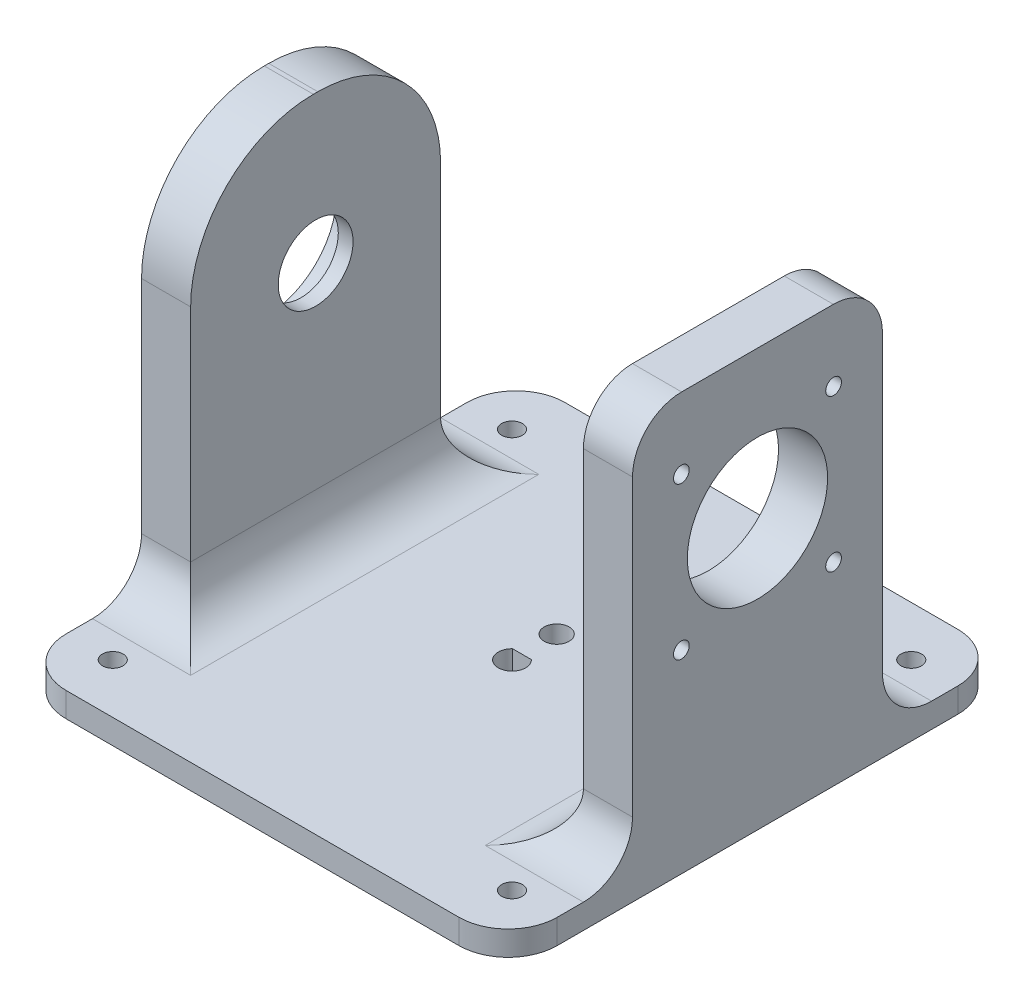
SolidWorks part; units mm, degrees
ref_plane "Front Plane" through (0, 0, 0) normal (0, 0, 1) x (1, 0, 0)
ref_plane "Top Plane" through (0, 0, 0) normal (0, 1, 0) x (1, 0, 0)
ref_plane "Right Plane" through (0, 0, 0) normal (1, 0, 0) x (0, 0, -1)
sketch "Sketch2" plane through (0, 0, 0) normal (0, 1, 0) x (1, 0, 0)
  line L1 (-50, 50.8) -> (50, 50.8)
  line L2 (-50, 50.8) -> (-50, -50.8)
  line L3 (-50, -50.8) -> (50, -50.8)
  line L4 (50, 50.8) -> (50, -50.8)
  line L5 (-50, 50.8) -> (50, -50.8) construction
  line L6 (-50, -50.8) -> (50, 50.8) construction
  line L7 (-50, 50.8) -> (-40, 50.8)
  line L8 (-50, 50.8) -> (-50, -50.8)
  line L9 (-50, -50.8) -> (-40, -50.8)
  line L10 (-40, 50.8) -> (-40, -50.8)
  line L11 (50, 50.8) -> (40, 50.8)
  line L12 (50, 50.8) -> (50, -50.8)
  line L13 (50, -50.8) -> (40, -50.8)
  line L14 (40, 50.8) -> (40, -50.8)
  point P0 (0, 0)
  dimension "D1" = 101.6
  dimension "D2" = 100
  dimension "D3" = 10
  dimension "D4" = 10
extrude "Boss-Extrude1" add sketch "Sketch2" along normal blind 80 contours L10 L1 L2 L3 | L1 L14 L3 L4 region at (-45, 0, 0) region at (45, 0, 0)
extrude "Boss-Extrude2" add sketch "Sketch2<3>" against normal blind 5 contours L1 L14 L3 L4 | L14 L1 L10 L3 | L10 L1 L2 L3 region at (-45, 0, 0) region at (0, 0, 0) region at (45, 0, 0)
sketch "Sketch2<3>" plane through (0, 0, 0) normal (0, 1, 0) x (1, 0, 0) same geometry as "Sketch2"
sketch "Sketch3" plane through (-50, 0, 0) normal (-1, 0, 0) x (0, 0, 1)
  line L0 (0, 80) -> (0, -5) construction
  line L1 (-50.8, 80) -> (50.8, 80) construction
  line L2 (-50.8, -5) -> (50.8, -5) construction
  circle A0 centre (0, 50) radius 14.2875
  dimension "D1" = 28.575
  dimension "D2" = 30
extrude "Cut-Extrude1" cut sketch "Sketch3" against normal blind 117
sketch "Sketch4" plane through (50, 0, 0) normal (1, 0, 0) x (0, 0, -1)
  line L0 (-25.4543, 80) -> (-25.4543, 0)
  line L1 (50.8, 80) -> (-50.8, 80) construction
  line L2 (-25.4543, 0) -> (-50.8, 0)
  line L3 (-50.8, -5) -> (-50.8, 80) construction
  line L4 (0, 80) -> (0, -5) construction
  line L5 (50.8, -5) -> (-50.8, -5) construction
  line L6 (25.4543, 0) -> (50.8, 0)
  line L7 (25.4543, 80) -> (25.4543, 0)
  line L8 (-25.4543, 80) -> (-50.8, 80)
  line L9 (-50.8, 80) -> (-50.8, 0)
  line L10 (25.4543, 80) -> (50.8, 80)
  line L11 (50.8, 80) -> (50.8, 0)
  dimension "D1" = 0
extrude "Cut-Extrude2" cut sketch "Sketch4" against normal blind 119
fillet "Fillet3" radius 10 8 edges at (40, 0, 0) (-40, 0, 0) (-45, 0, -25.4543) (-45, 0, 25.4543) (45, 0, 25.4543) (45, 0, -25.4543) (45, 80, 25.4543) (45, 80, -25.4543)
sketch "Sketch5" plane through (0, 0, 0) normal (0, 1, 0) x (1, 0, 0)
  line L1 (-1.9177, 2.032) -> (1.9177, 2.032)
  arc A0 (-1.9177, 2.032) -> (1.9177, 2.032) centre (0, 0) ccw
  dimension "D1" = 5.588
  dimension "D2" = 2.032
fillet "Fillet2" radius 10 4 edges at (50, -2.5, -50.8) (-50, -2.5, -50.8) (50, -2.5, 50.8) (-50, -2.5, 50.8)
sketch "Sketch7" plane through (50, 0, 0) normal (1, 0, 0) x (0, 0, -1)
  line L0 (0, 87.6521) -> (0, 12.3479) construction
  line L1 (-24.8111, 50) -> (24.8111, 50) construction
  circle A0 centre (-15.5, 65.5) radius 1.6
  circle A1 centre (15.5, 65.5) radius 1.6
  circle A2 centre (15.5, 34.5) radius 1.6
  circle A3 centre (-15.5, 34.5) radius 1.6
  point P5 (0, 50)
  point P8 (0, 50)
  dimension "D1" = 3.2
  dimension "D2" = 15.5
  dimension "D3" = 15.5
extrude "Cut-Extrude4" cut sketch "Sketch7" against normal blind 21
sketch "Sketch8" plane through (40, 0, 0) normal (-1, 0, 0) x (0, 0, 1)
  circle A0 centre (0, 50) radius 14.2875
  circle A1 centre (0, 50) radius 7.62
  dimension "D1" = 15.24
extrude "Boss-Extrude3" add sketch "Sketch8" along normal blind 3 from surface starting at face at (-40, 45, 0)
sketch "Sketch9" plane through (0, -5, 0) normal (0, -1, 0) x (1, 0, 0)
  line L0 (0, 50.8) -> (0, -50.8) construction
  line L2 (-40, -50.8) -> (40, -50.8) construction
  line L3 (-50, 0) -> (50, 0) construction
  line L5 (50, -40.8) -> (50, 40.8) construction
  circle A0 centre (-40.66, 40.66) radius 2.1
  circle A1 centre (40.66, 40.66) radius 2.1
  circle A2 centre (-40.66, -40.66) radius 2.1
  circle A3 centre (40.66, -40.66) radius 2.1
  point P4 (0, 0)
  point P10 (0, 0)
  dimension "D1" = 4.2
  dimension "D2" = 40.66
  dimension "D3" = 40.66
extrude "Cut-Extrude5" cut sketch "Sketch9" against normal up to surface (5 mm away) up to face at (0, 0, 0)
extrude "Cut-Extrude6" cut sketch "Sketch5" against normal blind 10
sketch "Sketch10" plane through (0, 0, 0) normal (0, 1, 0) x (1, 0, 0)
  circle A0 centre (0, 9.0998) radius 2.54
extrude "Cut-Extrude7" cut sketch "Sketch10" against normal blind 10
fillet "Fillet4" radius 25 2 edges at (-45, 80, -25.4543) (-45, 80, 25.4543)
